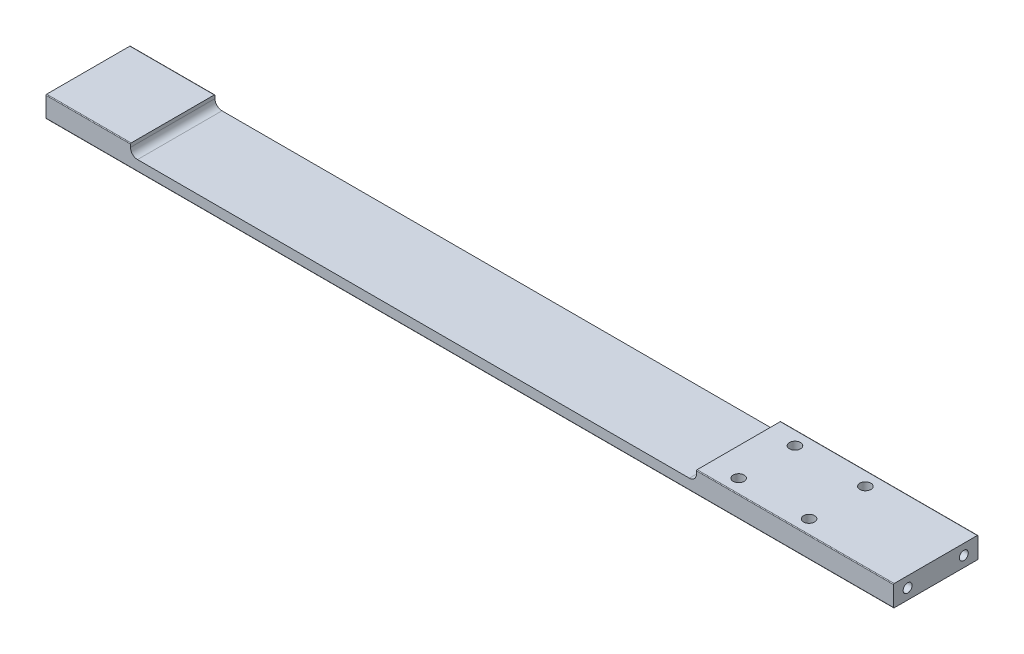
SolidWorks part; units mm, degrees
ref_plane "Front Plane" through (0, 0, 0) normal (0, 0, 1) x (1, 0, 0)
ref_plane "Top Plane" through (0, 0, 0) normal (0, 1, 0) x (1, 0, 0)
ref_plane "Right Plane" through (0, 0, 0) normal (1, 0, 0) x (0, 0, -1)
sketch "Sketch1" plane through (0, 0, 0) normal (0, 1, 0) x (1, 0, 0)
  line L1 (191.135, -19.05) -> (-191.135, -19.05)
  line L2 (191.135, -19.05) -> (191.135, 19.05)
  line L3 (191.135, 19.05) -> (-191.135, 19.05)
  line L4 (-191.135, -19.05) -> (-191.135, 19.05)
  line L5 (191.135, -19.05) -> (-191.135, 19.05) construction
  line L6 (191.135, 19.05) -> (-191.135, -19.05) construction
  point P0 (0, 0)
  dimension "Length" = 382.27
  dimension "Width" = 38.1
sketch "Sketch2" plane through (0, 0, 0) normal (1, 0, 0) x (0, 0, -1)
  line L0 (19.05, 4.7625) -> (19.05, -4.7625) construction
  point P2 (19.05, 0)
  dimension "Thickness" = 9.525
sketch "Sketch3" plane through (0, 0, 0) normal (0, 1, 0) x (1, 0, 0)
  line L1 (-191.135, 19.05) -> (191.135, 19.05)
  line L2 (-191.135, 19.05) -> (-191.135, -19.05)
  line L3 (-191.135, -19.05) -> (191.135, -19.05)
  line L4 (191.135, 19.05) -> (191.135, -19.05)
extrude "Boss-Extrude1" add sketch "Sketch3" against normal up to vertex (4.7625 mm away) and the other way up to vertex (4.7625 mm away) up to point (0, -4.7625, -19.05) other way up to point (0, 4.7625, -19.05)
fillet "Fillet1" radius 0.3143 4 edges at (0, -4.7625, 19.05) (0, -4.7625, -19.05) (0, 4.7625, -19.05) (0, 4.7625, 19.05)
sketch "Sketch4" plane through (-191.135, 0, 0) normal (-1, 0, 0) x (0, 0, 1)
  line L0 (0, 0) -> (12.7, 0) construction
  line L1 (0, 0) -> (-12.6447, 0) construction
hole_wizard "Tap Drill for #10-32 Tap1" positions "Sketch5" profile "Sketch6" hole size "#10-32" standard "ANSI Inch"
sketch "Sketch5" plane through (-191.135, 0, 0) normal (-1, 0, 0) x (0, 0, 1)
  point P0 (-12.6447, 0)
  point P3 (12.7, 0)
sketch "Sketch6" plane through (-191.135, 0, -12.6447) normal (0, 1, 0) x (0, 0, 1)
  line L0 (0, 0) -> (0, 26.6133)
  line L1 (0, 26.6133) -> (2.0193, 25.4)
  line L2 (2.0193, 25.4) -> (2.0193, 0)
  line L5 (2.0193, 0) -> (0, 0)
  line L10 (0, 26.6133) -> (-2.0193, 25.4) construction
  line L11 (0, -6.35) -> (0, 107.95) construction
  dimension "Hole Dia." = 4.0386
  dimension "Hole Depth" = 25.4
  dimension "Drill Angle" = 118
hole_wizard "Tap Drill for #10-32 Tap2" positions "Sketch7" profile "Sketch8" hole size "#10-32" standard "ANSI Inch"
sketch "Sketch7" plane through (191.135, 0, 0) normal (1, 0, 0) x (0, 0, -1)
  point P0 (-12.7, 0)
  point P3 (12.6447, 0)
sketch "Sketch8" plane through (191.135, 0, 12.7) normal (0, 1, 0) x (0, 0, -1)
  line L0 (0, 0) -> (0, 26.6133)
  line L1 (0, 26.6133) -> (2.0193, 25.4)
  line L2 (2.0193, 25.4) -> (2.0193, 0)
  line L5 (2.0193, 0) -> (0, 0)
  line L10 (0, 26.6133) -> (-2.0193, 25.4) construction
  line L11 (0, -6.35) -> (0, 107.95) construction
  dimension "Hole Dia." = 4.0386
  dimension "Hole Depth" = 25.4
  dimension "Drill Angle" = 118
sketch "Sketch10" plane through (0, 0, -19.05) normal (0, 0, -1) x (-1, 0, 0)
  line L0 (153.035, 4.7625) -> (153.035, 3.175)
  line L1 (-191.135, 4.7625) -> (191.135, 4.7625) construction
  line L2 (149.86, 0) -> (-99.06, 0)
  line L3 (-102.235, 3.175) -> (-102.235, 4.7625)
  line L4 (-102.235, 4.7625) -> (153.035, 4.7625)
  line L5 (-191.135, -4.7625) -> (-191.135, 78.7988) construction
  line L6 (191.135, -4.7625) -> (191.135, 78.7988) construction
  arc A0 (153.035, 3.175) -> (149.86, 0) centre (149.86, 3.175) cw
  arc A1 (-99.06, 0) -> (-102.235, 3.175) centre (-99.06, 3.175) cw
  point P12 (153.035, 0)
  dimension "D4" = 3.175
  dimension "D1" = 88.9
  dimension "D2" = 38.1
  dimension "D3" = 4.7625
extrude "Cut-Extrude1" cut sketch "Sketch10" against normal through all
sketch "Sketch13" plane through (0, -4.7625, 0) normal (0, -1, 0) x (1, 0, 0)
  line L0 (191.135, 0) -> (146.685, 0) construction
  line L1 (191.135, 18.7357) -> (191.135, -18.7357) construction
  line L2 (146.685, 0) -> (146.685, 12.7) construction
  line L3 (146.685, 12.7) -> (114.935, 12.7) construction
  line L4 (114.935, 12.7) -> (114.935, -12.7) construction
  line L5 (114.935, -12.7) -> (146.685, -12.7) construction
  line L6 (146.685, -12.7) -> (146.685, 0) construction
  dimension "D1" = 44.45
  dimension "D2" = 31.75
  dimension "D3" = 31.75
hole_wizard "#10 Clearance Hole1" positions "Sketch14" profile "Sketch15" hole size "#10" standard "ANSI Inch" end condition through all
sketch "Sketch14" plane through (0, -4.7625, 0) normal (0, -1, 0) x (-1, 0, 0)
  point P0 (-114.935, 12.7)
  point P3 (-146.685, 12.7)
  point P6 (-146.685, -12.7)
  point P9 (-114.935, -12.7)
sketch "Sketch15" plane through (114.935, -4.7625, -12.7) normal (1, 0, 0) x (0, 0, -1)
  line L0 (0, 0) -> (0, 9.525)
  line L1 (0, 9.525) -> (2.4892, 9.525)
  line L2 (2.4892, 9.525) -> (2.4892, 3.1411)
  line L3 (2.4892, 3.1411) -> (5.2197, 0)
  line L5 (5.2197, 0) -> (0, 0)
  line L6 (-2.4892, 3.1411) -> (-5.2197, 0) construction
  line L11 (0, -6.35) -> (0, 107.95) construction
  dimension "Thru Hole Dia." = 4.9784
  dimension "Thru Hole Depth" = 9.525
  dimension "Near C'Sink Dia." = 10.4394
  dimension "Near C'Sink Angle" = 82
equation "\"D1@Fillet1\" = \"Thickness@Sketch2\" * .033"
